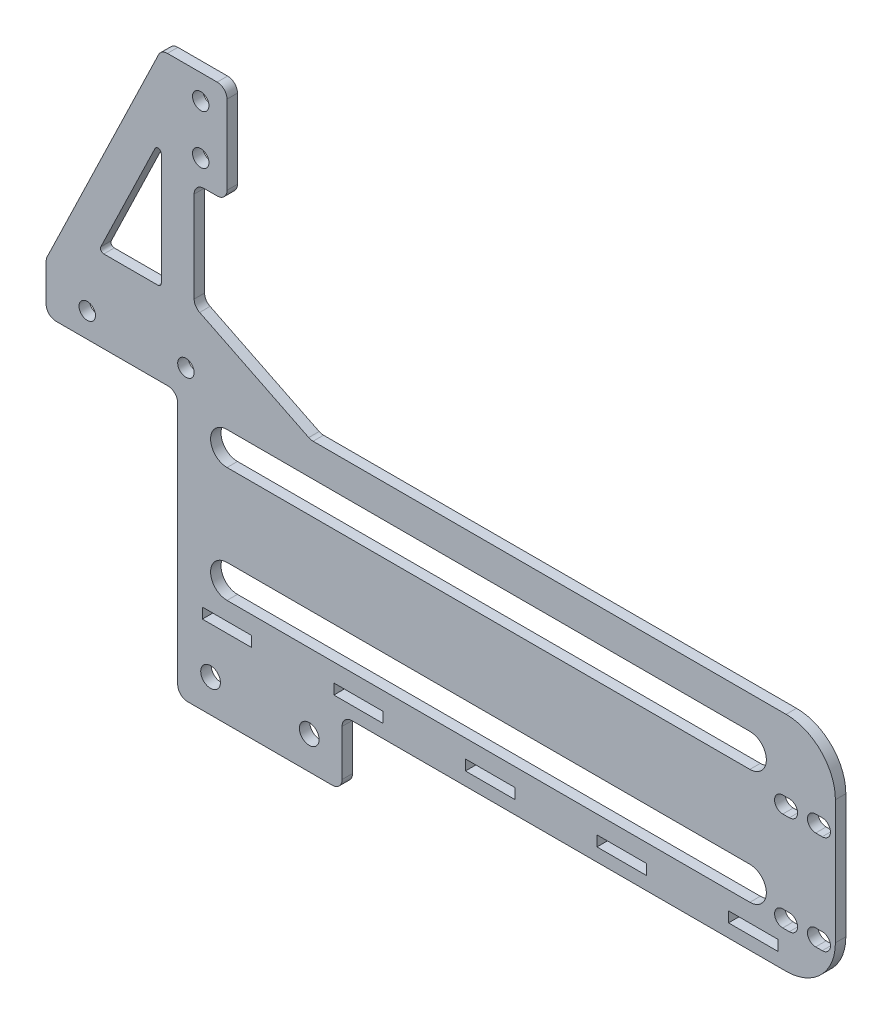
SolidWorks part; units mm, degrees
material "1060 Alloy"
ref_plane "Front Plane" through (0, 0, 0) normal (0, 0, 1) x (1, 0, 0)
ref_plane "Top Plane" through (0, 0, 0) normal (0, 1, 0) x (1, 0, 0)
ref_plane "Right Plane" through (0, 0, 0) normal (1, 0, 0) x (0, 0, -1)
sketch "Sketch1" plane through (0, 0, 0) normal (0, 0, 1) x (1, 0, 0)
  line L1 (-4.1933, -88) -> (25.47, -95.5)
  line L2 (25.47, -95.5) -> (185, -95.5)
  line L5 (185, -95.5) -> (185, -143.5)
  line L6 (167.5, -156) -> (152.5, -156)
  line L7 (32.5, -156) -> (32.5, -159.175)
  line L9 (7.5, -159.175) -> (7.5, -156)
  line L12 (-55, -88) -> (-55, -103)
  line L13 (-55, -103) -> (-15, -103)
  line L15 (-7.5, -156) -> (7.5, -156)
  line L22 (72.5, -156) -> (72.5, -159.175)
  line L24 (47.5, -159.175) -> (47.5, -156)
  line L25 (112.5, -156) -> (112.5, -159.175)
  line L27 (87.5, -159.175) -> (87.5, -156)
  line L28 (152.5, -156) -> (152.5, -159.175)
  line L30 (127.5, -159.175) -> (127.5, -156)
  line L31 (47.5, -156) -> (32.5, -156)
  line L32 (87.5, -156) -> (72.5, -156)
  line L33 (127.5, -156) -> (112.5, -156)
  line L36 (-7.5, -159.175) -> (-7.5, -156)
  line L37 (-7.5, -159.175) -> (7.5, -159.175) construction
  line L38 (-55, -88) -> (-4.1933, -88)
  line L47 (-15, -150.03) -> (-15, -103)
  line L48 (190.8745, -134.75) -> (169.5, -134.75) construction
  line L49 (185, -114.75) -> (185, -154.75) construction
  line L50 (181, -119.75) -> (179, -119.75) construction
  line L51 (181, -122.25) -> (179, -122.25)
  line L52 (181, -117.25) -> (179, -117.25)
  line L53 (171, -119.75) -> (169, -119.75) construction
  line L54 (171, -122.25) -> (169, -122.25)
  line L55 (171, -117.25) -> (169, -117.25)
  line L56 (185, -143.5) -> (185, -148.5)
  line L57 (-7.5, -159.175) -> (7.5, -159.175)
  line L58 (-15, -150.03) -> (-15, -163.175)
  line L60 (185, -148.5) -> (185, -163.175)
  line L61 (167.5, -156) -> (167.5, -159.175)
  line L62 (32.5, -159.175) -> (47.5, -159.175)
  line L63 (72.5, -159.175) -> (87.5, -159.175)
  line L64 (152.5, -159.175) -> (167.5, -159.175)
  line L65 (112.5, -159.175) -> (127.5, -159.175)
  line L66 (171, -149.75) -> (169, -149.75) construction
  line L67 (171, -147.25) -> (169, -147.25)
  line L68 (171, -152.25) -> (169, -152.25)
  line L69 (181, -149.75) -> (179, -149.75) construction
  line L70 (181, -147.25) -> (179, -147.25)
  line L71 (181, -152.25) -> (179, -152.25)
  line L72 (10, -14.8748) -> (10, -181.5625) construction
  line L74 (-15, -163.175) -> (-15, -183.175)
  line L75 (-15, -183.175) -> (35, -183.175)
  line L76 (35, -163.175) -> (35, -183.175)
  line L77 (-5, -173.175) -> (25, -173.175) construction
  line L78 (-42.5, -95.5) -> (-12.5, -95.5) construction
  line L79 (35, -163.175) -> (185, -163.175)
  arc A9 (181, -122.25) -> (181, -117.25) centre (181, -119.75) ccw
  arc A10 (179, -117.25) -> (179, -122.25) centre (179, -119.75) ccw
  arc A11 (171, -122.25) -> (171, -117.25) centre (171, -119.75) ccw
  arc A12 (169, -117.25) -> (169, -122.25) centre (169, -119.75) ccw
  arc A13 (171, -147.25) -> (171, -152.25) centre (171, -149.75) cw
  arc A14 (169, -152.25) -> (169, -147.25) centre (169, -149.75) cw
  arc A15 (181, -147.25) -> (181, -152.25) centre (181, -149.75) cw
  arc A16 (179, -152.25) -> (179, -147.25) centre (179, -149.75) cw
  circle A17 centre (-5, -173.175) radius 3
  circle A18 centre (25, -173.175) radius 3
  circle A19 centre (-42.5, -95.5) radius 2.5
  circle A20 centre (-12.5, -95.5) radius 2.5
  point P13 (180, -119.75)
  point P26 (170, -119.75)
  point P45 (40, -156)
  point P69 (170, -149.75)
  point P76 (180, -149.75)
  point P89 (10, -183.175)
  point P94 (35, -173.175)
  point P95 (10, -173.175)
  point P99 (-55, -95.5)
  dimension "D8" = 2
  dimension "D25" = 6
  dimension "D10" = 5
  dimension "40" = 40
  dimension "D3" = 24.25
  dimension "D4" = 7.5
  dimension "D5" = 15
  dimension "D6" = 5
  dimension "D7" = 4
  dimension "D9" = 10
  dimension "D13" = 7.5
  dimension "D15" = 25
  dimension "D16" = 3.175
  dimension "D17" = 15
  dimension "D19" = 15
  dimension "D20" = 53
  dimension "D21" = 200
  dimension "D22" = 50
  dimension "D23" = 20
  dimension "D24" = 30
  dimension "D26" = 30
  dimension "D27" = 12.5
  dimension "D18" = 4
base flange "Base-Flange1" sketch "Sketch1" thickness 3.175 reverse thickness direction no parameters "D1"=0.7366
sketch "Sketch2" plane through (0, 0, 0) normal (0, 0, 1) x (1, 0, 0)
  line L0 (0, -110.5) -> (159, -110.5) construction
  line L1 (0, -105.5) -> (159, -105.5)
  line L2 (0, -115.5) -> (159, -115.5)
  line L3 (0, -145.5) -> (159, -145.5) construction
  line L4 (0, -140.5) -> (159, -140.5)
  line L5 (0, -150.5) -> (159, -150.5)
  line L6 (-15, -103) -> (-15, -183.175) construction
  line L7 (185, -95.5) -> (25.47, -95.5) construction
  line L8 (185, -163.175) -> (185, -95.5) construction
  arc A0 (0, -105.5) -> (0, -115.5) centre (0, -110.5) ccw
  arc A1 (159, -115.5) -> (159, -105.5) centre (159, -110.5) ccw
  arc A2 (0, -140.5) -> (0, -150.5) centre (0, -145.5) ccw
  arc A3 (159, -150.5) -> (159, -140.5) centre (159, -145.5) ccw
  point P2 (79.5, -110.5)
  point P7 (79.5, -145.5)
  dimension "D1" = 35
  dimension "D2" = 15
  dimension "D3" = 15
  dimension "D4" = 10
  dimension "D5" = 26
extrude "Cut-Extrude1" cut sketch "Sketch2" against normal blind 10 normal cut yes
sketch "Sketch3" plane through (0, 0, 0) normal (0, 0, 1) x (1, 0, 0)
  line L0 (-55, -88) -> (-20, -15.5)
  line L1 (-4.1933, -88) -> (-55, -88) construction
  line L2 (-55, -88) -> (-55, -103) construction
  line L3 (-20, -15.5) -> (-10, -15.5)
  line L4 (-10, -45.5) -> (-10, -78)
  line L5 (-10, -88) -> (-55, -88)
  line L6 (-20, -78) -> (-39.0681, -78)
  line L7 (-39.0681, -78) -> (-20, -38.5018)
  line L8 (-20, -38.5018) -> (-20, -38.5018)
  line L9 (-20, -38.5018) -> (-20, -78)
  line L10 (25.47, -95.5) -> (-10, -78)
  line L13 (-10, -88) -> (25.47, -95.5)
  line L16 (185, -95.5) -> (25.47, -95.5) construction
  line L17 (-10, -15.5) -> (-10, -88) construction
  line L18 (-10, -15.5) -> (0, -15.5)
  line L20 (-10, -45.5) -> (0, -45.5)
  line L21 (0, -15.5) -> (0, -45.5)
  dimension "D1" = 72.5
  dimension "D2" = 10
  dimension "D4" = 45
  dimension "D6" = 30
  dimension "D7" = 10
  dimension "D3" = 10
extrude "Boss-Extrude1" add sketch "Sketch3" against normal up to surface (3.175 mm away)
fillet "Fillet2" radius 3 12 edges at (25.47, -95.5, -1.5875) (35, -163.175, -1.5875) (35, -183.175, -1.5875) (-15, -183.175, -1.5875) (-15, -103, -1.5875) (-55, -103, -1.5875) (-55, -88, -1.5875) (0, -45.5, -1.5875) (0, -15.5, -1.5875) (-20, -15.5, -1.5875) (-10, -78, -1.5875) (-10, -45.5, -1.5875)
fillet "Fillet1" radius 15 2 edges at (185, -95.5, -1.5875) (185, -163.175, -1.5875)
fillet "Fillet3" radius 1 3 edges at (-39.0681, -78, -1.5875) (-20, -38.5018, -1.5875) (-20, -78, -1.5875)
sketch "Sketch4" plane through (0, 0, 0) normal (0, 0, 1) x (1, 0, 0)
  line L0 (-8, -23) -> (-8, -38) construction
  line L2 (0, -18.5) -> (0, -42.5) construction
  line L3 (0, -18.5) -> (0, -42.5) construction
  circle A0 centre (-8, -23) radius 2.5
  circle A1 centre (-8, -38) radius 2.5
  point P7 (-8, -30.5)
  point P10 (0, -30.5)
  dimension "D1" = 5
  dimension "D2" = 15
  dimension "D3" = 8
extrude "Cut-Extrude2" cut sketch "Sketch4" against normal blind 10 normal cut yes
sketch "Sketch5" plane through (0, 0, 0) normal (0, 0, 1) x (1, 0, 0)
  line L1 (-11.8483, -83.3831) -> (-5.5431, -83.3831)
  line L2 (-11.8483, -83.3831) -> (-11.8483, -89.9308)
  line L3 (-11.8483, -89.9308) -> (-5.5431, -89.9308)
  line L4 (-5.5431, -83.3831) -> (-5.5431, -89.9308)
extrude "Boss-Extrude2" add sketch "Sketch5" against normal up to surface (3.175 mm away) up to face at (-10.5, -23, -3.175)
sketch "Bend-Lines1" [suppressed] plane through (0, 0, 0) normal (0, 1, 0) x (1, 0, 0)
sketch "Bounding-Box1" [suppressed] plane through (0, 0, 0) normal (0, 1, 0) x (1, 0, 0)
sheet metal parameters "Sheet-Metal1" thickness 3.175 parameters "D1"=0.7366
flat pattern "Flat-Pattern1" [suppressed]
sketch "Bend-Lines2" plane through (0, 0, 0) normal (0, 1, 0) x (1, 0, 0)
sketch3d "Bounding-Box2" [suppressed]
  line L0 (-55, -172.205, 0) -> (185, -172.205, 0) construction
  line L1 (-55, -68.5, 0) -> (185, -68.5, 0) construction
  line L2 (-55, -172.205, 0) -> (-55, -68.5, 0) construction
  line L3 (185, -172.205, 0) -> (185, -68.5, 0) construction
sheet metal parameters "Sheet-Metal5" thickness 3.175 parameters "D1"=0.7366
flat pattern "Flat-Pattern1"
sketch "Bend-Lines2" plane through (0, 0, 0) normal (0, 1, 0) x (1, 0, 0)
sketch3d "Bounding-Box2" [suppressed]
  line L0 (-55, -88, 0) -> (185, -88, 0) construction
  line L1 (-55, -183.175, 0) -> (185, -183.175, 0) construction
  line L2 (-55, -88, 0) -> (-55, -183.175, 0) construction
  line L3 (185, -88, 0) -> (185, -183.175, 0) construction
sheet metal parameters "Sheet-Metal6" thickness 3.175 parameters "D1"=0.7366
flat pattern "Flat-Pattern1"
sketch "Bend-Lines2" plane through (0, 0, 0) normal (0, 1, 0) x (1, 0, 0)
sketch3d "Bounding-Box2" [suppressed]
  line L0 (-18.5854, -8.1033, 0) -> (204.0823, -109.5437, 0) construction
  line L1 (-82.5349, -148.4764, 0) -> (140.1328, -249.9168, 0) construction
  line L2 (-18.5854, -8.1033, 0) -> (-82.5349, -148.4764, 0) construction
  line L3 (204.0823, -109.5437, 0) -> (140.1328, -249.9168, 0) construction
sheet metal parameters "Sheet-Metal7" thickness 3.175 parameters "D1"=0.7366
flat pattern "Flat-Pattern1"
sketch "Bend-Lines2" plane through (0, 0, 0) normal (0, 1, 0) x (1, 0, 0)
sketch3d "Bounding-Box2" [suppressed]
  line L0 (-18.5854, -8.1033, 0) -> (204.0823, -109.5437, 0) construction
  line L1 (-83.6145, -150.8462, 0) -> (139.0532, -252.2866, 0) construction
  line L2 (-18.5854, -8.1033, 0) -> (-83.6145, -150.8462, 0) construction
  line L3 (204.0823, -109.5437, 0) -> (139.0532, -252.2866, 0) construction
sheet metal parameters "Sheet-Metal8" thickness 3.175 parameters "D1"=0.7366
flat pattern "Flat-Pattern1"
sketch "Bend-Lines2" plane through (0, 0, 0) normal (0, 1, 0) x (1, 0, 0)
sketch3d "Bounding-Box2" [suppressed]
  line L0 (-18.5854, -8.1033, 0) -> (204.0823, -109.5437, 0) construction
  line L1 (-83.6145, -150.8462, 0) -> (139.0532, -252.2866, 0) construction
  line L2 (-18.5854, -8.1033, 0) -> (-83.6145, -150.8462, 0) construction
  line L3 (204.0823, -109.5437, 0) -> (139.0532, -252.2866, 0) construction
